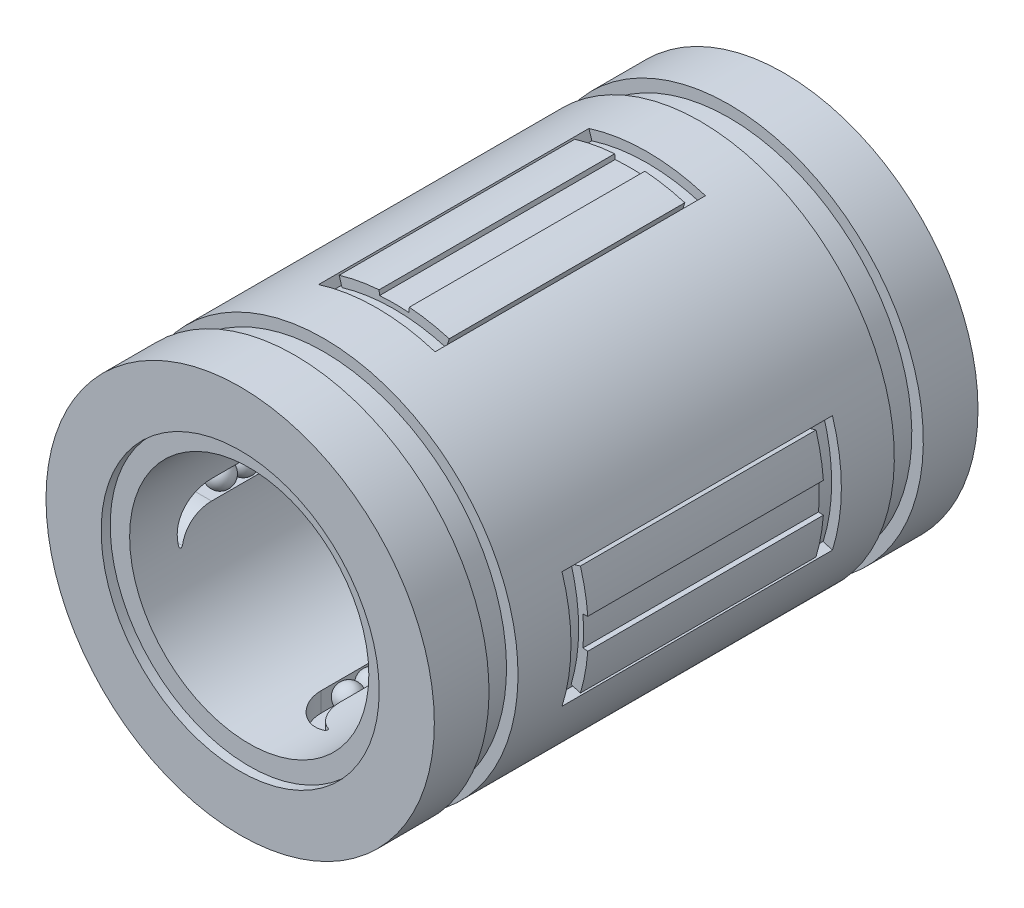
SolidWorks part; units mm, degrees
ref_plane "Front Plane" through (0, 0, 0) normal (0, 0, 1) x (1, 0, 0)
ref_plane "Top Plane" through (0, 0, 0) normal (0, 1, 0) x (1, 0, 0)
ref_plane "Right Plane" through (0, 0, 0) normal (1, 0, 0) x (0, 0, -1)
sketch "Sketch1" plane through (0, 0, 0) normal (0, 0, 1) x (1, 0, 0)
  line L0 (2.3813, 7.5719) -> (2.2622, 7.1933)
  line L1 (-2.3813, 7.5719) -> (-2.2622, 7.1933)
  line L2 (0, 0) -> (0, 7.9375) construction
  line L3 (-4.8734, 0.3969) -> (-4.8734, -0.3969) construction
  line L4 (-5.6694, -0.3969) -> (-5.6694, 0.3969) construction
  line L5 (-4.8734, 0) -> (-5.6694, 0) construction
  line L6 (-5.2714, 0.5089) -> (-5.2714, -0.5089)
  line L7 (-2.2487, 7.6123) -> (-2.1363, 7.2317)
  line L8 (-0.6169, 7.9135) -> (-0.6015, 7.7157)
  line L9 (2.2487, 7.6123) -> (2.1363, 7.2317)
  line L10 (0.6169, 7.9135) -> (0.6015, 7.7157)
  line L11 (0, 25.4) -> (5.8282, 19.5718) construction
  line L12 (0, 25.4) -> (-5.8282, 19.5718) construction
  line L13 (5.8282, 19.5718) -> (6.0437, 19.3563)
  line L14 (-5.8282, 19.5718) -> (-6.0437, 19.3563)
  circle A0 centre (0, 0) radius 7.9375
  arc A1 (2.2622, 7.1933) -> (-2.2622, 7.1933) centre (0, 0) ccw
  circle A2 centre (0, 0) radius 4.8895
  circle A3 centre (0, 0) radius 4.7625 construction
  circle A4 centre (0, 0) radius 5.6833
  arc A5 (-5.2714, -0.5089) -> (-5.2714, 0.5089) centre (-5.2714, 0) ccw
  arc A7 (0.6015, 7.7157) -> (-0.6015, 7.7157) centre (0, 0) ccw
  arc A8 (5.8282, 19.5718) -> (-5.8282, 19.5718) centre (0, 25.4) ccw
  arc A9 (6.0437, 19.3563) -> (-6.0437, 19.3563) centre (0, 25.4) ccw
  dimension "OD" = 15.875
  dimension "ID" = 9.525
  dimension "Ring OD" = 17.0942
  dimension "D1" = 4.7625
  dimension "D2" = 0.3969
  dimension "D3" = 0.127
  dimension "D4" = 0.7937
  dimension "D5" = 0.7937
  dimension "D6" = 1
  dimension "D7" = 1
  dimension "D9" = 12
  dimension "D10" = 12
  dimension "D8" = 0.1984
  dimension "D11" = 90
  dimension "Offset" = 25.4
  dimension "D12" = 0.3048
sketch "Sketch2" plane through (0, 0, 0) normal (1, 0, 0) x (0, 0, -1)
  line L0 (11.1125, 0) -> (-11.1125, 0)
  line L1 (5.5266, 7.9375) -> (-5.5266, 7.9375)
  line L2 (8.2846, 7.9375) -> (8.2846, 7.4676) construction
  line L3 (0, 7.0244) -> (0, -7.0244) construction
  line L4 (-7.4083, -0.3969) -> (7.4083, -0.3969)
  line L6 (-7.4083, 0.3969) -> (7.4083, 0.3969)
  line L8 (-7.4083, -0.3969) -> (7.4083, 0.3969) construction
  line L9 (-7.4083, 0.3969) -> (7.4083, -0.3969) construction
  line L11 (0, 7.9375) -> (0, -7.9375) construction
  line L13 (-8.8773, 7.9375) -> (-7.692, 7.9375)
  line L14 (-8.8773, 7.9375) -> (-8.8773, 7.4676)
  line L15 (-8.8773, 7.4676) -> (-7.692, 7.4676)
  line L16 (-7.692, 7.9375) -> (-7.692, 7.4676)
  line L17 (7.692, 7.9375) -> (8.8773, 7.9375)
  line L18 (7.692, 7.9375) -> (7.692, 7.4676)
  line L19 (7.692, 7.4676) -> (8.8773, 7.4676)
  line L20 (8.8773, 7.9375) -> (8.8773, 7.4676)
  arc A0 (7.4083, 0.3969) -> (8.8846, -1.2114) centre (7.4083, -1.0848) cw
  arc A1 (7.4083, -0.3969) -> (8.744, -1.2372) centre (7.4083, -1.8785) cw
  arc A2 (8.744, -1.2372) -> (8.8846, -1.2114) centre (8.8108, -1.2051) ccw
  arc A3 (-7.4083, 0.3969) -> (-8.8846, -1.2114) centre (-7.4083, -1.0848) ccw
  arc A4 (-8.744, -1.2372) -> (-8.8846, -1.2114) centre (-8.8108, -1.2051) cw
  arc A5 (-7.4083, -0.3969) -> (-8.744, -1.2372) centre (-7.4083, -1.8785) ccw
  point P0 (-10.7421, 0)
  point P4 (0, 0)
  point P9 (0, 7.9375)
  point P10 (0, 0)
  point P20 (0, 0)
  point P37 (-4.8154, 7.9375)
  point P38 (4.8154, 7.9375)
  point P39 (7.8401, 7.9375)
  point P40 (8.7291, 7.9375)
  dimension "D4" = 0.7937
  dimension "D5" = 1.4817
  dimension "D6" = 1.4817
  dimension "D7" = 0.0741
  dimension "Overall Length" = 22.225
  dimension "D1" = 11.0532
  dimension "D2" = 0.3704
  dimension "D3" = 7.4083
  dimension "Groove Depth" = 0.4699
  dimension "C" = 17.7546
  dimension "D9" = 1.1853
  dimension "D8" = 9.6308
  dimension "D10" = 0.889
sketch "Sketch3" plane through (0, 0, 0) normal (0, 0, 1) x (1, 0, 0)
  circle A0 centre (0, 0) radius 7.9375 construction
  circle A1 centre (0, 0) radius 4.8895 construction
  circle A2 centre (0, 0) radius 7.9375
  circle A3 centre (0, 0) radius 4.8895
extrude "Boss-Extrude1" add sketch "Sketch3" along normal mid plane 22.225
sketch "Sketch4" plane through (0, 0, 11.1125) normal (0, 0, 1) x (1, 0, 0)
  circle A0 centre (0, 0) radius 4.8895 construction
  circle A1 centre (0, 0) radius 5.6833 construction
  circle A2 centre (0, 0) radius 4.8895
  circle A3 centre (0, 0) radius 5.6833
extrude "Cut-Extrude1" cut sketch "Sketch4" against normal up to vertex (0.3704 mm away) up to point (0, 0, 10.7421)
mirror "Mirror1" about plane through (0, 0, 0) normal (0, 0, 1) of "Cut-Extrude1"
sketch "Sketch5" plane through (0, 0, 0) normal (0, 0, 1) x (1, 0, 0)
  line L0 (-2.3813, 7.5719) -> (-2.2622, 7.1933) construction
  line L1 (2.3813, 7.5719) -> (2.2622, 7.1933) construction
  line L2 (-2.3813, 7.5719) -> (-2.2622, 7.1933)
  line L3 (2.3813, 7.5719) -> (2.2622, 7.1933)
  circle A0 centre (0, 0) radius 7.9375 construction
  arc A1 (2.2622, 7.1933) -> (-2.2622, 7.1933) centre (0, 0) ccw construction
  arc A2 (2.3813, 7.5719) -> (-2.3813, 7.5719) centre (0, 0) ccw
  arc A3 (2.2622, 7.1933) -> (-2.2622, 7.1933) centre (0, 0) ccw
extrude "Cut-Extrude2" cut sketch "Sketch5" against normal up to vertex (5.5266 mm away) and the other way up to vertex (5.5266 mm away) up to point (0, 7.9375, -5.5266) other way up to point (0, 7.9375, 5.5266)
sketch "Sketch6" plane through (0, 0, 0) normal (0, 0, 1) x (1, 0, 0)
  line L0 (2.2487, 7.6123) -> (2.1363, 7.2317) construction
  line L1 (0.6169, 7.9135) -> (0.6015, 7.7157) construction
  line L2 (-0.6169, 7.9135) -> (-0.6015, 7.7157) construction
  line L3 (-2.2487, 7.6123) -> (-2.1363, 7.2317) construction
  line L4 (2.2487, 7.6123) -> (2.1363, 7.2317)
  line L5 (0.6169, 7.9135) -> (0.6015, 7.7157)
  line L6 (-0.6169, 7.9135) -> (-0.6015, 7.7157)
  line L7 (-2.2487, 7.6123) -> (-2.1363, 7.2317)
  circle A0 centre (0, 0) radius 7.9375 construction
  arc A1 (2.2622, 7.1933) -> (-2.2622, 7.1933) centre (0, 0) ccw construction
  arc A2 (0.6015, 7.7157) -> (-0.6015, 7.7157) centre (0, 0) ccw construction
  arc A3 (2.2487, 7.6123) -> (0.6169, 7.9135) centre (0, 0) ccw
  arc A4 (2.1363, 7.2317) -> (-2.1363, 7.2317) centre (0, 0) ccw
  arc A5 (0.6015, 7.7157) -> (-0.6015, 7.7157) centre (0, 0) ccw
  arc A6 (-0.6169, 7.9135) -> (-2.2487, 7.6123) centre (0, 0) ccw
extrude "Boss-Extrude2" add sketch "Sketch6" along normal up to vertex (4.8154 mm away) and the other way up to vertex (4.8154 mm away) up to point (0, 7.9375, 4.8154) other way up to point (0, 7.9375, -4.8154)
sketch "Sketch7" plane through (0, 0, 0) normal (1, 0, 0) x (0, 0, -1)
  line L0 (-7.4083, -0.3969) -> (7.4083, -0.3969) construction
  line L1 (-7.4083, 0.3969) -> (7.4083, 0.3969) construction
  line L2 (-7.4083, -0.3969) -> (7.4083, -0.3969)
  line L3 (-7.4083, 0.3969) -> (7.4083, 0.3969)
  arc A0 (8.744, -1.2372) -> (7.4083, -0.3969) centre (7.4083, -1.8785) ccw construction
  arc A1 (8.744, -1.2372) -> (8.8846, -1.2114) centre (8.8108, -1.2051) ccw construction
  arc A2 (8.8846, -1.2114) -> (7.4083, 0.3969) centre (7.4083, -1.0848) ccw construction
  arc A3 (-7.4083, 0.3969) -> (-8.8846, -1.2114) centre (-7.4083, -1.0848) ccw construction
  arc A4 (-8.8846, -1.2114) -> (-8.744, -1.2372) centre (-8.8108, -1.2051) ccw construction
  arc A5 (-7.4083, -0.3969) -> (-8.744, -1.2372) centre (-7.4083, -1.8785) ccw construction
  arc A6 (8.744, -1.2372) -> (7.4083, -0.3969) centre (7.4083, -1.8785) ccw
  arc A7 (8.744, -1.2372) -> (8.8846, -1.2114) centre (8.8108, -1.2051) ccw
  arc A8 (8.8846, -1.2114) -> (7.4083, 0.3969) centre (7.4083, -1.0848) ccw
  arc A9 (-7.4083, 0.3969) -> (-8.8846, -1.2114) centre (-7.4083, -1.0848) ccw
  arc A10 (-8.8846, -1.2114) -> (-8.744, -1.2372) centre (-8.8108, -1.2051) ccw
  arc A11 (-7.4083, -0.3969) -> (-8.744, -1.2372) centre (-7.4083, -1.8785) ccw
extrude "Cut-Extrude3" cut sketch "Sketch7" against normal up to surface (5.6694 mm away) up to face at (5.6833, 0, 10.7421)
sketch "Sketch8" plane through (0, 0, 0) normal (0, 0, 1) x (1, 0, 0)
  line L0 (-5.2714, 0.5089) -> (-5.2714, -0.5089) construction
  line L1 (-5.2714, 0.5089) -> (-5.2714, -0.5089)
  arc A0 (-5.2714, -0.5089) -> (-5.2714, 0.5089) centre (-5.2714, 0) ccw construction
  arc A1 (-5.2714, -0.5089) -> (-5.2714, 0.5089) centre (-5.2714, 0) ccw
revolve "Revolve1" add sketch "Sketch8" angle 360 about L1
pattern_linear "LPattern1" count 8 spacing 0.9525 along (0, 0, -1) of "Revolve1"
mirror "Mirror2" about plane through (0, 0, 0) normal (0, 0, 1) of "LPattern1"
pattern_circular "CirPattern1" count 4 over 360 about axis through (0, 0, 11.1125) along (0, 0, -1) of "Boss-Extrude2", "Cut-Extrude3", "Revolve1", "LPattern1", "Mirror2"
pattern_circular "CirPattern2" count 4 over 360 about axis through (0, 0, 11.1125) along (0, 0, -1) of "Cut-Extrude2", "Boss-Extrude2" reverse direction yes
sketch "Sketch9" plane through (0, 0, 0) normal (1, 0, 0) x (0, 0, -1)
  line L0 (8.8773, 7.9375) -> (8.8773, 7.4676) construction
  line L1 (7.692, 7.4676) -> (8.8773, 7.4676) construction
  line L2 (7.692, 7.9375) -> (7.692, 7.4676) construction
  line L3 (7.692, 7.9375) -> (8.8773, 7.9375) construction
  line L4 (-7.692, 7.9375) -> (-7.692, 7.4676) construction
  line L5 (-8.8773, 7.4676) -> (-7.692, 7.4676) construction
  line L6 (-8.8773, 7.9375) -> (-8.8773, 7.4676) construction
  line L7 (-8.8773, 7.9375) -> (-7.692, 7.9375) construction
  line L8 (8.8773, 7.9375) -> (8.8773, 7.4676)
  line L9 (7.692, 7.4676) -> (8.8773, 7.4676)
  line L10 (7.692, 7.9375) -> (7.692, 7.4676)
  line L11 (7.692, 7.9375) -> (8.8773, 7.9375)
  line L12 (-7.692, 7.9375) -> (-7.692, 7.4676)
  line L13 (-8.8773, 7.4676) -> (-7.692, 7.4676)
  line L14 (-8.8773, 7.9375) -> (-8.8773, 7.4676)
  line L15 (-8.8773, 7.9375) -> (-7.692, 7.9375)
revolve "Cut-Revolve1" cut sketch "Sketch9" angle 360 about L0
ref_plane "Plane1" through (0, 0, -8.2846) normal (0, 0, -1) x (-1, 0, 0)
equation "\"D1@Sketch1\"=\"OD@Sketch1\"*.3"
equation "\"D2@Sketch1\"=\"OD@Sketch1\"*.025"
equation "\"D1@Sketch2\"=\"Overall Length@Sketch2\"* .4973333333"
equation "\"D4@Sketch1\"=\"OD@Sketch1\"*.05"
equation "\"D2@Sketch2\"=\"Overall Length@Sketch2\"* .01666667"
equation "\"D3@Sketch2\"=\"Overall Length@Sketch2\"* .333333333333"
equation "\"D4@Sketch2\"=\"OD@Sketch1\" * .05"
equation "\"D5@Sketch2\"=\"D3@Sketch2\"* .2"
equation "\"D6@Sketch2\"=\"D5@Sketch2\""
equation "\"D7@Sketch2\"=\"D6@Sketch2\"* .05"
equation "\"D5@Sketch1\"=\"OD@Sketch1\" * .05"
equation "\"D8@Sketch1\"=\"D2@Sketch1\"/2"
equation "\"D9@Sketch2\"=\"Overall Length@Sketch2\" * .0533333333"
equation "\"D1@Boss-Extrude1\"=\"Overall Length@Sketch2\""
equation "\"D8@Sketch2\"=\"Overall Length@Sketch2\" * .4333333333"
